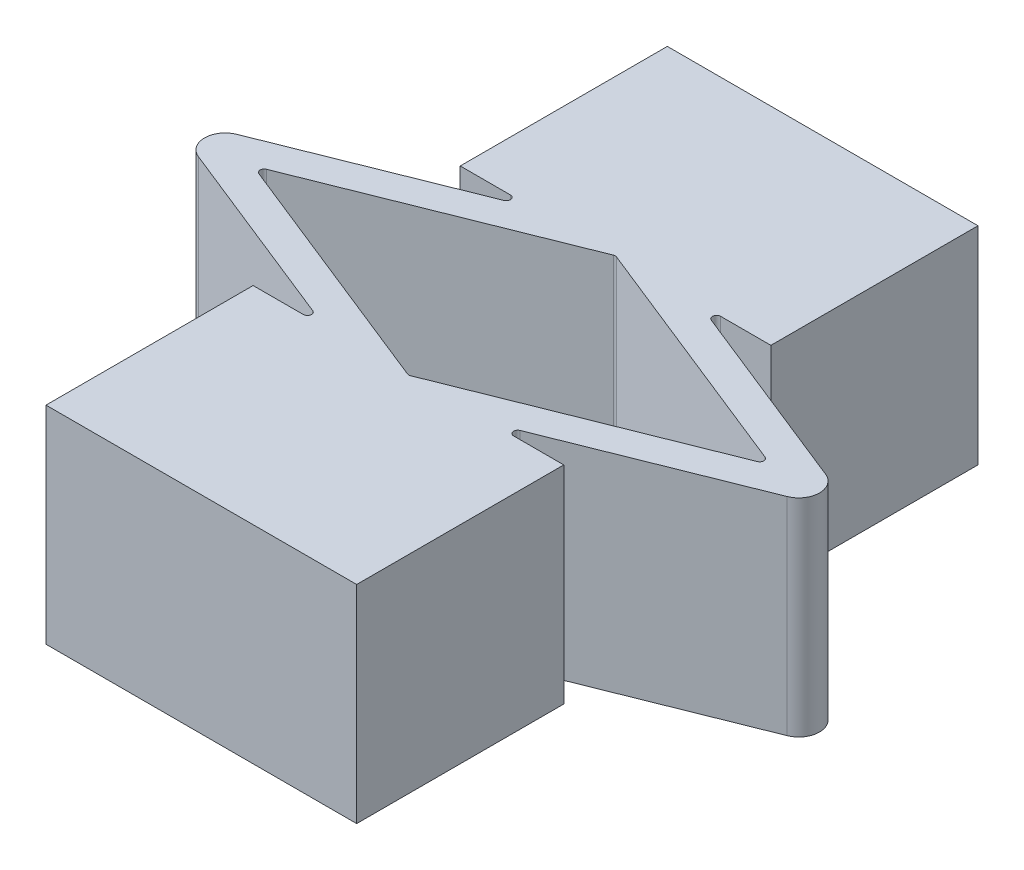
SolidWorks part; units mm, degrees
ref_plane "Front Plane" through (0, 0, 0) normal (0, 0, 1) x (1, 0, 0)
ref_plane "Top Plane" through (0, 0, 0) normal (0, 1, 0) x (1, 0, 0)
ref_plane "Right Plane" through (0, 0, 0) normal (1, 0, 0) x (0, 0, -1)
sketch "Sketch1" plane through (0, 0, 0) normal (0, 1, 0) x (1, 0, 0)
  line L0 (0, 15) -> (-12.5, 10)
  line L1 (-7.5, -5) -> (7.5, -5)
  line L2 (-7.5, -5) -> (-7.5, 5)
  line L3 (-7.5, 5) -> (7.5, 5)
  line L4 (7.5, -5) -> (7.5, 5)
  line L5 (-7.5, -5) -> (7.5, 5) construction
  line L6 (-7.5, 5) -> (7.5, -5) construction
  line L7 (-7.5, 15) -> (7.5, 15)
  line L8 (-7.5, 15) -> (-7.5, 25)
  line L9 (-7.5, 25) -> (7.5, 25)
  line L10 (7.5, 15) -> (7.5, 25)
  line L11 (-7.5, 15) -> (7.5, 25) construction
  line L12 (-7.5, 25) -> (7.5, 15) construction
  line L13 (-12.5, 10) -> (0, 5)
  line L14 (-4.0389, 15) -> (-16.5389, 10)
  line L15 (-16.5389, 10) -> (-4.0389, 5)
  line L16 (0, 20) -> (0, 0) construction
  point P0 (0, 0)
  point P6 (0, 20)
  point P17 (0, 10)
  dimension "D1" = 10
  dimension "D2" = 15
  dimension "D3" = 10
  dimension "D4" = 15
  dimension "D5" = 20
  dimension "D6" = 25
  dimension "D7" = 1.5
extrude "Boss-Extrude2" add sketch "Sketch1" along normal blind 10 contours L7 L10 L9 L8 | L1 L4 L3 L2 region at (0, 0, -20) region at (0, 0, 0)
extrude "Boss-Extrude3" add sketch "Sketch1<4>" along normal blind 10 contours L14 L15 L3 L13 L0 L7 region at (-6.3218, 0, -12.6794)
sketch "Sketch1<4>" plane through (0, 0, 0) normal (0, 1, 0) x (1, 0, 0) same geometry as "Sketch1"
ref_plane "Plane1" through (0, 0, 0) normal (-1, 0, 0) x (0, 0, 1)
mirror "Mirror1" about plane through (0, 0, 0) normal (-1, 0, 0) of "Boss-Extrude3"
fillet "Fillet1" radius 0.2 8 edges at (4.0389, 5, -5) (4.0389, 5, -15) (-4.0389, 5, -15) (-4.0389, 5, -5) (0, 5, -5) (12.5, 5, -10) (0, 5, -15) (-12.5, 5, -10)
fillet "Fillet2" radius 1 2 edges at (16.5389, 5, -10) (-16.5389, 5, -10)
